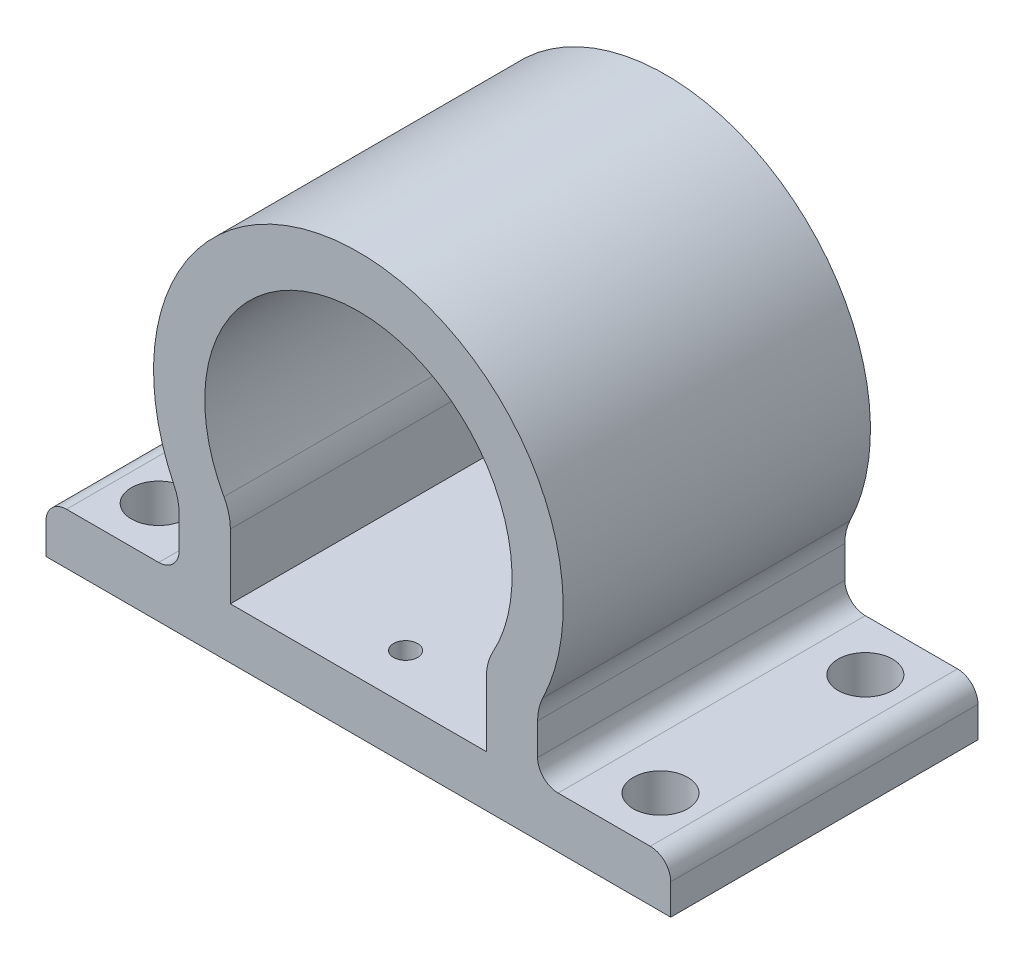
SolidWorks part; units mm, degrees
material "Markforged Onyx"
ref_plane "Front Plane" through (0, 0, 0) normal (0, 0, 1) x (1, 0, 0)
ref_plane "Top Plane" through (0, 0, 0) normal (0, 1, 0) x (1, 0, 0)
ref_plane "Right Plane" through (0, 0, 0) normal (1, 0, 0) x (0, 0, -1)
sketch "Sketch1" plane through (0, 0, 0) normal (0, 0, 1) x (1, 0, 0)
  line L0 (-15.875, -20.32) -> (15.875, -20.32)
  line L1 (-15.875, -20.32) -> (-15.875, -10.5303)
  line L2 (15.875, -20.32) -> (15.875, -10.5303)
  line L3 (22.225, -26.67) -> (22.225, -12.2967)
  line L4 (-22.225, -26.67) -> (22.225, -26.67)
  line L5 (-22.225, -26.67) -> (-22.225, -12.2967)
  arc A0 (-15.875, -10.5303) -> (15.875, -10.5303) centre (0, 0) cw
  arc A1 (-22.225, -12.2967) -> (22.225, -12.2967) centre (0, 0) cw
  point P7 (0, 19.05)
  dimension "D2" = 19.05
  dimension "D1" = 6.35
  dimension "D3" = 31.75
  dimension "D4" = 39.37
extrude "Boss-Extrude1" add sketch "Sketch1" along normal blind 38.1
fillet "Fillet1" radius 6.35 4 edges at (22.225, -12.2967, 19.05) (15.875, -10.5303, 19.05) (-22.225, -12.2967, 19.05) (-15.875, -10.5303, 19.05)
sketch "Sketch2" plane through (0, -26.67, 0) normal (0, -1, 0) x (1, 0, 0)
  line L0 (0, 38.1) -> (0, 0) construction
  line L3 (-22.225, 19.05) -> (22.225, 19.05) construction
  line L10 (-22.225, 38.1) -> (-22.225, 0) construction
  line L11 (-22.225, 0) -> (22.225, 0) construction
  line L12 (22.225, 38.1) -> (22.225, 0) construction
  line L13 (-22.225, 38.1) -> (22.225, 38.1) construction
  circle A0 centre (0, 22.7471) radius 9.5 construction
  circle A1 centre (0, 32.2471) radius 1.7
  circle A2 centre (0, 13.2471) radius 1.7
  circle A3 centre (0, 32.2471) radius 3
  circle A4 centre (0, 13.2471) radius 3
  point P2 (0, 0)
  point P3 (0, 0)
  point P5 (0, 0)
  point P6 (0, 0)
  point P9 (0, 0)
  point P11 (0, 0)
  point P12 (0, 0)
  point P15 (0, 19.05)
  point P21 (0, 0)
  point P22 (0, 0)
  point P24 (0, 0)
  point P25 (0, 0)
  point P27 (0, 0)
  point P29 (0, 0)
  point P30 (0, 0)
  point P33 (0, 0)
  dimension "D1" = 19
  dimension "D3" = 3.4
  dimension "D4" = 6
  dimension "D2" = 3.6971
extrude "Cut-Extrude1" cut sketch "Sketch2" against normal up to next contours A1 | A2 region at (0, -26.67, 32.2471) region at (0, -26.67, 13.2471)
extrude "Cut-Extrude2" cut sketch "Sketch2<3>" against normal blind 6.35
sketch "Sketch2<3>" plane through (0, -26.67, 0) normal (0, -1, 0) x (1, 0, 0) same geometry as "Sketch2"
sketch "Sketch5" plane through (-22.225, 0, 0) normal (-1, 0, 0) x (0, 0, 1)
  line L0 (0, -13.8395) -> (0, -26.67) construction
  line L5 (0, -20.32) -> (38.1, -20.32)
  line L7 (0, -20.32) -> (0, -26.67)
  line L8 (0, -26.67) -> (38.1, -26.67)
  line L9 (38.1, -20.32) -> (38.1, -26.67)
  line L10 (0, -20.32) -> (38.1, -26.67) construction
  line L11 (0, -26.67) -> (38.1, -20.32) construction
  line L12 (38.1, -13.8395) -> (38.1, -26.67) construction
  line L14 (38.1, -26.67) -> (0, -26.67) construction
  point P4 (19.05, -23.495)
  dimension "D1" = 6.35
extrude "Boss-Extrude3" add sketch "Sketch5" along normal blind 16.51
sketch "Sketch6" plane through (0, -26.67, 0) normal (0, -1, 0) x (-1, 0, 0)
  line L0 (31.115, -6.35) -> (31.115, -31.75) construction
  line L1 (31.115, -19.05) -> (38.735, -19.05) construction
  line L2 (38.735, -38.1) -> (38.735, 0) construction
  circle A0 centre (31.115, -6.35) radius 3.3782
  circle A1 centre (31.115, -31.75) radius 3.3782
  dimension "D1" = 6.7564
  dimension "D2" = 25.4
  dimension "D3" = 7.62
extrude "Cut-Extrude3" cut sketch "Sketch6" against normal through all
mirror "Mirror1" about plane through (0, 0, 0) normal (1, 0, 0) of "Cut-Extrude3", "Boss-Extrude3"
fillet "Fillet2" radius 2.54 4 edges at (38.735, -20.32, 19.05) (22.225, -20.32, 19.05) (-38.735, -20.32, 19.05) (-22.225, -20.32, 19.05)
sketch "Sketch7" plane through (0, -20.32, 0) normal (0, 1, 0) x (1, 0, 0)
  circle A0 centre (0, -13.2471) radius 3 construction
  circle A1 centre (0, -13.2471) radius 3
  circle A3 centre (0, -13.2471) radius 1.5
  circle A4 centre (0, -32.2471) radius 3 construction
  circle A5 centre (0, -32.2471) radius 3
  circle A6 centre (0, -32.2471) radius 1.5
  dimension "D1" = 3
extrude "Boss-Extrude4" add sketch "Sketch7" against normal blind 2.54
